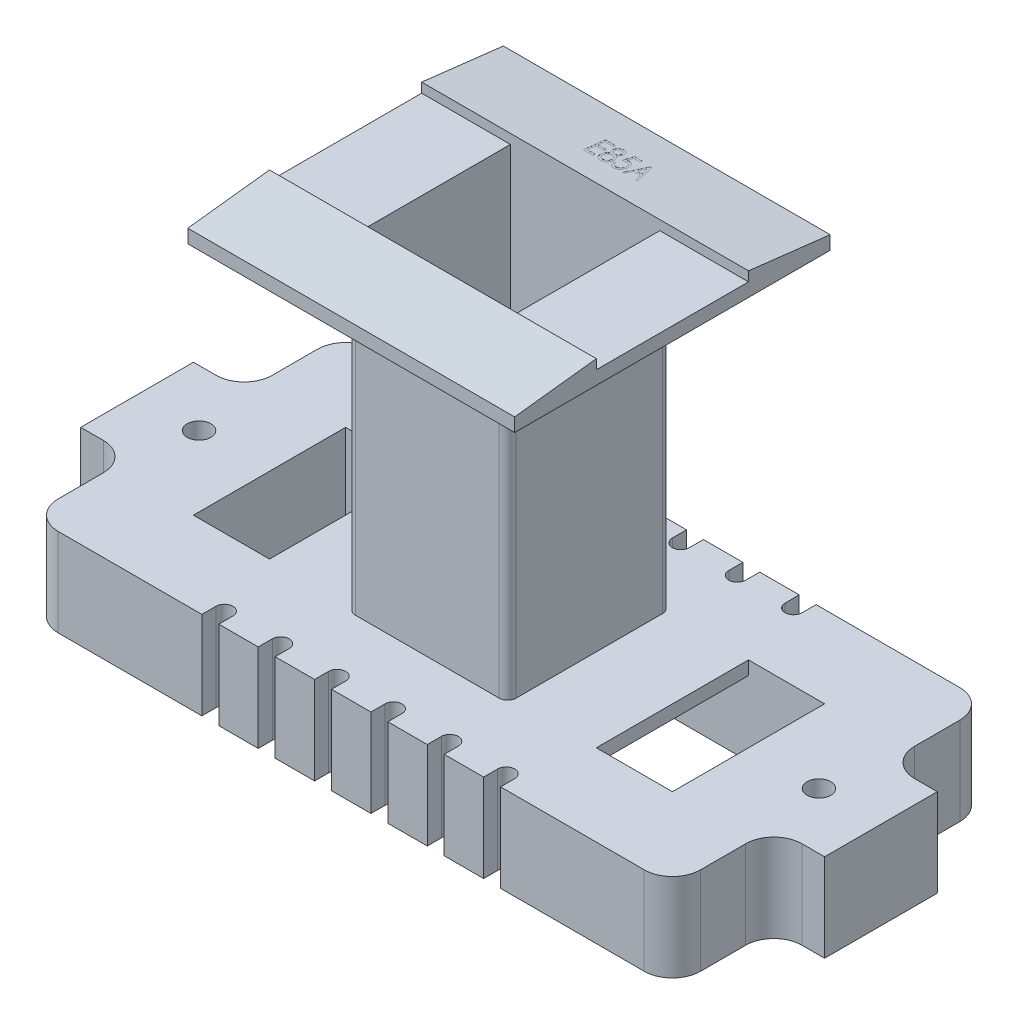
SolidWorks part; units mm, degrees
material "ABS"
ref_plane "Front Plane" through (0, 0, 0) normal (0, 0, 1) x (1, 0, 0)
ref_plane "Top Plane" through (0, 0, 0) normal (0, 1, 0) x (1, 0, 0)
ref_plane "Right Plane" through (0, 0, 0) normal (1, 0, 0) x (0, 0, -1)
sketch "Sketch2" plane through (0, 0, 0) normal (0, 1, 0) x (1, 0, 0)
  line L0 (14.25, -14.5) -> (14.25, 14.5)
  line L5 (13.25, -13.5) -> (-13.25, -13.5)
  line L6 (13.25, -13.5) -> (13.25, 13.5)
  line L11 (13.25, 13.5) -> (-13.25, 13.5)
  line L12 (-13.25, -13.5) -> (-13.25, 13.5)
  line L13 (13.25, -13.5) -> (-13.25, 13.5) construction
  line L14 (13.25, 13.5) -> (-13.25, -13.5) construction
  line L15 (14.25, 14.5) -> (-14.25, 14.5)
  line L16 (-14.25, -14.5) -> (-14.25, 14.5)
  line L17 (14.25, -14.5) -> (-14.25, -14.5)
  point P0 (0, 0)
  point P1 (0, 0)
  point P5 (0, 0)
  dimension "D1" = 27
  dimension "D2" = 26.5
  dimension "D3" = 1
extrude "Boss-Extrude1" add sketch "Sketch2" along normal mid plane 55.7
sketch "Sketch4" plane through (0, 27.85, 0) normal (0, 1, 0) x (1, 0, 0)
  line L1 (-29, -28) -> (29, -28)
  line L2 (-29, -28) -> (-29, 28)
  line L3 (-29, 28) -> (29, 28)
  line L4 (29, -28) -> (29, 28)
  line L5 (-29, -28) -> (29, 28) construction
  line L6 (-29, 28) -> (29, -28) construction
  line L14 (13.25, -13.5) -> (13.25, 13.5) construction
  line L15 (-13.25, -13.5) -> (13.25, -13.5) construction
  line L16 (-13.25, 13.5) -> (-13.25, -13.5) construction
  line L17 (13.25, 13.5) -> (-13.25, 13.5) construction
  line L18 (13.25, -13.5) -> (13.25, 13.5)
  line L19 (-13.25, -13.5) -> (13.25, -13.5)
  line L20 (-13.25, 13.5) -> (-13.25, -13.5)
  line L21 (13.25, 13.5) -> (-13.25, 13.5)
  point P0 (0, 0)
  dimension "D1" = 58
  dimension "D2" = 56
extrude "Boss-Extrude2" add sketch "Sketch4" along normal blind 2.4
mirror "Mirror1" about plane through (0, 0, 0) normal (0, 1, 0) of "Boss-Extrude2"
fillet "Fillet1" radius 1.5 4 edges at (-14.25, 0, 14.5) (-14.25, 0, -14.5) (14.25, 0, -14.5) (14.25, 0, 14.5)
sketch "Sketch5" plane through (0, 0, 0) normal (1, 0, 0) x (0, 0, -1)
  line L0 (-28, 30.25) -> (-13.5, 31.95)
  line L1 (-13.5, 31.95) -> (-13.5, 30.25)
  line L2 (-28, 30.25) -> (28, 30.25) construction
  line L4 (-13.5, 30.25) -> (-28, 30.25)
  line L5 (0, 0) -> (0, 38.1311) construction
  line L7 (28, 30.25) -> (13.5, 31.95)
  line L8 (13.5, 30.25) -> (28, 30.25)
  line L10 (-13.5, 30.25) -> (-13.5, -30.25) construction
  line L11 (13.5, 31.95) -> (13.5, 30.25)
  dimension "D1" = 1.7
extrude "Boss-Extrude3" add sketch "Sketch5" along normal mid plane 58
sketch "Sketch9" plane through (0, 33.0781, -3.8781) normal (0, 0.9932, -0.1164) x (1, 0, 0)
  line L0 (-29, 14.1878) -> (29, 14.1878) construction
  line L1 (-29, 24.2871) -> (-29, 9.6878) construction
  line L2 (29, 24.2871) -> (29, 9.6878) construction
  line L4 (29, 9.6878) -> (-29, 9.6878) construction
  text T0 "E85A" font "Century Gothic" height 4
  dimension "D1" = 4.5
extrude "Cut-Extrude2" cut sketch "Sketch9" against normal blind 0.01
sketch "Sketch8" plane through (0, -30.25, 0) normal (0, -1, 0) x (1, 0, 0)
  line L1 (-29, -28) -> (29, -28)
  line L2 (29, -28) -> (29, -13.5)
  line L37 (29, -13.5) -> (-29, -13.5)
  line L42 (-29, -13.5) -> (-29, -28)
  line L58 (0, 0) -> (37.0568, 0) construction
  line L79 (-29, 13.5) -> (-29, 28)
  line L82 (29, 13.5) -> (-29, 13.5)
  line L83 (29, 28) -> (29, 13.5)
  line L84 (-29, 28) -> (29, 28)
extrude "Boss-Extrude4" add sketch "Sketch8" along normal blind 13.2
sketch "Sketch11" plane through (0, -43.45, 0) normal (0, -1, 0) x (1, 0, 0)
  line L0 (0, 8.5975) -> (0, -6.374) construction
  line L3 (0, 0) -> (9.2559, 0) construction
  line L4 (29, 13.5) -> (42.5, 13.5)
  line L5 (29, -13.5) -> (42.5, -13.5)
  line L6 (42.5, 13.5) -> (42.5, -13.5)
  line L7 (29, 28) -> (29, 13.5)
  line L8 (13.25, 13.5) -> (29, 13.5) construction
  line L11 (29, -28) -> (29, -13.5)
  line L21 (29, 28) -> (52, 28)
  line L22 (57, 23) -> (57, 15)
  line L23 (62, 10) -> (66, 10)
  line L24 (66, -10) -> (66, 10)
  line L25 (62, -10) -> (66, -10)
  line L26 (57, -23) -> (57, -15)
  line L27 (29, -28) -> (52, -28)
  line L30 (-29, -28) -> (-52, -28)
  line L31 (-57, -23) -> (-57, -15)
  line L32 (-62, -10) -> (-66, -10)
  line L33 (-66, -10) -> (-66, 10)
  line L34 (-62, 10) -> (-66, 10)
  line L35 (-57, 23) -> (-57, 15)
  line L36 (-29, 28) -> (-52, 28)
  line L37 (-29, -28) -> (-29, -13.5)
  line L40 (-29, 28) -> (-29, 13.5)
  line L41 (-42.5, 13.5) -> (-42.5, -13.5)
  line L42 (-29, -13.5) -> (-42.5, -13.5)
  line L43 (-29, 13.5) -> (-42.5, 13.5)
  circle A3 centre (55, 0) radius 2.1
  arc A8 (52, -28) -> (57, -23) centre (52, -23) ccw
  arc A9 (57, -15) -> (62, -10) centre (62, -15) cw
  arc A10 (57, 23) -> (52, 28) centre (52, 23) ccw
  arc A11 (57, 15) -> (62, 10) centre (62, 15) ccw
  arc A14 (-57, 15) -> (-62, 10) centre (-62, 15) cw
  arc A15 (-57, 23) -> (-52, 28) centre (-52, 23) cw
  arc A16 (-57, -15) -> (-62, -10) centre (-62, -15) ccw
  arc A17 (-52, -28) -> (-57, -23) centre (-52, -23) cw
  circle A18 centre (-55, 0) radius 2.1
  point P4 (0, 0)
  point P5 (0, 0)
  point P6 (29.7122, 28)
  point P7 (29, 13.5)
  point P8 (0, 0)
  point P9 (0, 0)
  point P10 (29, -28)
  point P15 (0, 0)
  point P18 (-29.1436, -13.5)
  point P21 (0, 0)
  point P48 (66, 0)
  point P52 (57, -28)
  point P55 (57, -10)
  point P58 (57, 28)
  point P61 (57, 10)
  point P76 (-57, 10)
  point P77 (-57, 28)
  point P78 (-57, -10)
  point P79 (-57, -28)
  point P80 (-66, 0)
  dimension "D1" = 55
  dimension "D3" = 4.2
  dimension "D7" = 28
  dimension "D9" = 5
  dimension "D2" = 23.5
  dimension "D4" = 42.5
  dimension "D8" = 18
extrude "Boss-Extrude5" add sketch "Sketch11" against normal up to surface (15.6 mm away) up to face at (0, -27.85, 0)
sketch "Sketch7" plane through (0, -30.25, 0) normal (0, -1, 0) x (1, 0, 0)
  line L0 (0, 0) -> (0, 58.3367) construction
  line L2 (-29, -13.5) -> (-29, 13.5) construction
  line L7 (0, 0) -> (-44.9899, 0) construction
  line L23 (-29, 28) -> (29, 28) construction
  line L24 (-26.5, 25.5) -> (-26.5, 28)
  line L25 (-26.5, -25.5) -> (-26.5, -28)
  line L26 (-26.5, 28) -> (-23.5, 28)
  line L27 (-26.5, -28) -> (-23.5, -28)
  line L28 (-23.5, 28) -> (-23.5, 25.5)
  line L29 (-23.5, -28) -> (-23.5, -25.5)
  line L31 (-16.5, 25.5) -> (-16.5, 28)
  line L32 (-16.5, 28) -> (-13.5, 28)
  line L33 (-13.5, 28) -> (-13.5, 25.5)
  line L34 (-6.5, 25.5) -> (-6.5, 28)
  line L35 (-6.5, 28) -> (-3.5, 28)
  line L36 (-3.5, 28) -> (-3.5, 25.5)
  line L37 (3.5, 25.5) -> (3.5, 28)
  line L38 (3.5, 28) -> (6.5, 28)
  line L39 (6.5, 28) -> (6.5, 25.5)
  line L40 (13.5, 25.5) -> (13.5, 28)
  line L41 (13.5, 28) -> (16.5, 28)
  line L42 (16.5, 28) -> (16.5, 25.5)
  line L43 (23.5, 25.5) -> (23.5, 28)
  line L44 (23.5, 28) -> (26.5, 28)
  line L45 (26.5, 28) -> (26.5, 25.5)
  line L46 (-16.5, -25.5) -> (-16.5, -28)
  line L47 (-13.5, -28) -> (-13.5, -25.5)
  line L48 (-16.5, -28) -> (-13.5, -28)
  line L49 (-6.5, -25.5) -> (-6.5, -28)
  line L50 (-3.5, -28) -> (-3.5, -25.5)
  line L51 (-6.5, -28) -> (-3.5, -28)
  line L52 (3.5, -25.5) -> (3.5, -28)
  line L53 (6.5, -28) -> (6.5, -25.5)
  line L54 (3.5, -28) -> (6.5, -28)
  line L55 (13.5, -25.5) -> (13.5, -28)
  line L56 (16.5, -28) -> (16.5, -25.5)
  line L57 (13.5, -28) -> (16.5, -28)
  line L58 (23.5, -25.5) -> (23.5, -28)
  line L59 (26.5, -28) -> (26.5, -25.5)
  line L60 (23.5, -28) -> (26.5, -28)
  arc A0 (-26.5, 25.5) -> (-23.5, 25.5) centre (-25, 25.5) ccw
  arc A1 (-16.5, 25.5) -> (-13.5, 25.5) centre (-15, 25.5) ccw
  arc A2 (-6.5, 25.5) -> (-3.5, 25.5) centre (-5, 25.5) ccw
  arc A3 (3.5, 25.5) -> (6.5, 25.5) centre (5, 25.5) ccw
  arc A4 (13.5, 25.5) -> (16.5, 25.5) centre (15, 25.5) ccw
  arc A5 (23.5, 25.5) -> (26.5, 25.5) centre (25, 25.5) ccw
  arc A6 (23.5, -25.5) -> (26.5, -25.5) centre (25, -25.5) cw
  arc A7 (13.5, -25.5) -> (16.5, -25.5) centre (15, -25.5) cw
  arc A8 (3.5, -25.5) -> (6.5, -25.5) centre (5, -25.5) cw
  arc A9 (-6.5, -25.5) -> (-3.5, -25.5) centre (-5, -25.5) cw
  arc A10 (-16.5, -25.5) -> (-13.5, -25.5) centre (-15, -25.5) cw
  arc A11 (-26.5, -25.5) -> (-23.5, -25.5) centre (-25, -25.5) cw
  arc A12 (-23.5, 25.5) -> (-26.5, 25.5) centre (-25, 25.5) ccw construction
  arc A13 (-13.5, 25.5) -> (-16.5, 25.5) centre (-15, 25.5) ccw construction
  arc A14 (-3.5, 25.5) -> (-6.5, 25.5) centre (-5, 25.5) ccw construction
  arc A15 (6.5, 25.5) -> (3.5, 25.5) centre (5, 25.5) ccw construction
  arc A16 (16.5, 25.5) -> (13.5, 25.5) centre (15, 25.5) ccw construction
  arc A17 (26.5, 25.5) -> (23.5, 25.5) centre (25, 25.5) ccw construction
  arc A18 (-23.5, -25.5) -> (-26.5, -25.5) centre (-25, -25.5) cw construction
  arc A19 (-13.5, -25.5) -> (-16.5, -25.5) centre (-15, -25.5) cw construction
  arc A20 (-3.5, -25.5) -> (-6.5, -25.5) centre (-5, -25.5) cw construction
  arc A21 (6.5, -25.5) -> (3.5, -25.5) centre (5, -25.5) cw construction
  arc A22 (16.5, -25.5) -> (13.5, -25.5) centre (15, -25.5) cw construction
  arc A23 (26.5, -25.5) -> (23.5, -25.5) centre (25, -25.5) cw construction
  dimension "D1" = 3
  dimension "D6" = 6
  dimension "D2" = 4
  dimension "D3" = 2.5
  dimension "D4" = 6
  dimension "D5" = 2.5
  dimension "D7" = 6
extrude "Cut-Extrude1" cut sketch "Sketch7" against normal mid plane 33
